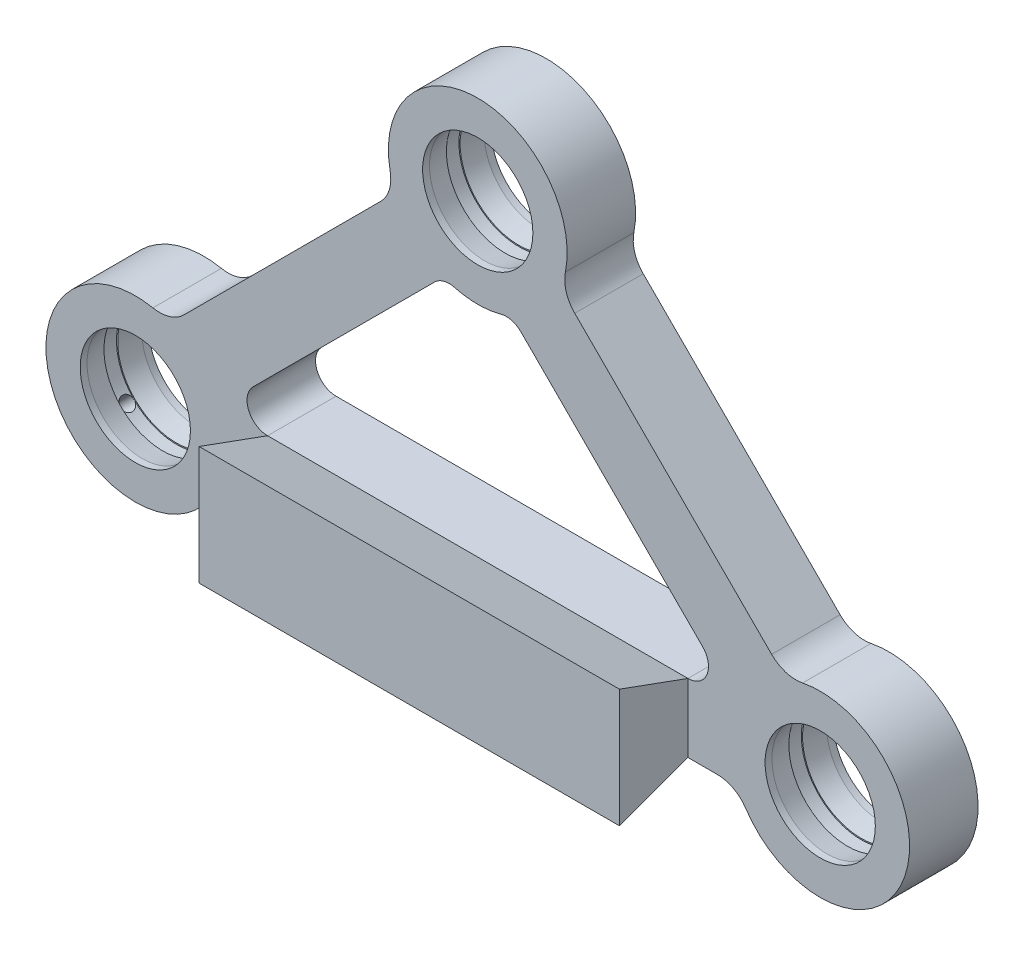
SolidWorks part; units mm, degrees
material "ABS"
ref_plane "Front Plane" through (0, 0, 0) normal (0, 0, 1) x (1, 0, 0)
ref_plane "Top Plane" through (0, 0, 0) normal (0, 1, 0) x (1, 0, 0)
ref_plane "Right Plane" through (0, 0, 0) normal (1, 0, 0) x (0, 0, -1)
sketch "Sketch1" plane through (0, 0, 0) normal (0, 0, 1) x (1, 0, 0)
  line L0 (-26.538, 0) -> (73.462, 0) construction
  line L2 (-26.538, 0) -> (23.462, 50) construction
  line L3 (23.462, 50) -> (73.462, 0) construction
  line L4 (-14.4839, 5) -> (61.4078, 5)
  line L5 (-14.4839, -5) -> (61.4078, -5)
  line L6 (-21.55, 12.0591) -> (11.4029, 45.012)
  line L7 (18.474, 37.9409) -> (-14.4789, 4.988)
  line L8 (28.45, 37.9409) -> (61.4029, 4.988)
  line L9 (35.5211, 45.012) -> (68.474, 12.0591)
  circle A0 centre (23.462, 50) radius 8.05
  circle A1 centre (73.462, 0) radius 8.05
  circle A2 centre (-26.538, 0) radius 8.05
  circle A3 centre (-26.538, 0) radius 13.05
  circle A4 centre (23.462, 50) radius 13.05
  circle A5 centre (73.462, 0) radius 13.05
  dimension "D1" = 16.1
  dimension "D2" = 16.1
  dimension "D3" = 16.1
  dimension "D4" = 45
  dimension "D5" = 45
  dimension "D6" = 100
  dimension "D7" = 5
  dimension "D8" = 5
  dimension "D9" = 5
  dimension "D10" = 5
  dimension "D11" = 5
  dimension "D12" = 5
  dimension "D13" = 5
  dimension "D14" = 5
  dimension "D15" = 5
extrude "Boss-Extrude1" add sketch "Sketch1" along normal blind 8 contours A3 A2 | A4 L6 A3 L4 L7 | A4 A0 | A5 L9 A4 L8 L4 | A5 L8 L4 L7 A3 L5 | A5 A1 | A3 L7 L4 | A5 L4 L8 region at (-1.538, 25, 0) region at (-14.4766, 4.996, 0) region at (-14.8224, 4.8528, 0) region at (23.462, 0, 0) region at (48.462, 25, 0) region at (61.4006, 4.996, 0) region at (14.4953, 41.0333, 0) region at (64.4997, 8.9712, 0)
sketch3d "3DSketch1" plane through (0, 0, 0) normal (0, 0, 1) x (1, 0, 0)
  dimension "D1" = 4
sketch "Sketch3" plane through (0, 0, 4) normal (0, 0, 1) x (1, 0, 0)
  circle A0 centre (-26.538, 0) radius 8.7553
  circle A1 centre (23.462, 50) radius 8.7553
  circle A2 centre (73.462, 0) radius 8.7553
  circle A3 centre (-26.538, 0) radius 8.05 construction
  circle A4 centre (23.462, 50) radius 8.05 construction
  circle A5 centre (73.462, 0) radius 8.05 construction
  dimension "D1" = 0.7053
  dimension "D2" = 0.7053
  dimension "D3" = 0.7053
extrude "Cut-Extrude1" cut sketch "Sketch3" against normal blind 1 and the other way blind 1 contours A1 | A0 | A2
sketch3d "3DSketch2" plane through (0, 0, 0) normal (0, 0, 1) x (1, 0, 0)
sketch3d "3DSketch3" plane through (0, 0, 0) normal (0, 0, 1) x (1, 0, 0)
  dimension "D1" = 26
sketch "Sketch4" plane through (0, 62.95, 0) normal (0, -1, 0) x (-1, 0, 0)
  line L0 (-41.8, -4) -> (41.8, -4) construction
  line L1 (-86.512, 0) -> (-86.512, -8) construction
  line L4 (-36.5118, -8) -> (-68.474, -8)
  line L5 (-36.5118, -8) -> (-68.474, -8)
  line L6 (-68.474, -8) -> (-86.512, -8)
  line L7 (-68.474, -8) -> (-86.512, -8)
  line L8 (-86.512, -8) -> (-86.512, 0)
  line L9 (-86.512, -8) -> (-86.512, 0)
  line L10 (-86.512, 0) -> (-68.474, 0)
  line L11 (-86.512, 0) -> (-68.474, 0)
  line L12 (-68.474, 0) -> (-36.5118, 0)
  line L13 (-68.474, 0) -> (-36.5118, 0)
  line L14 (-36.5118, 0) -> (-10.4122, 0)
  line L15 (-36.5118, 0) -> (-10.4122, 0)
  line L16 (-10.4122, 0) -> (21.55, 0)
  line L17 (-10.4122, 0) -> (21.55, 0)
  line L18 (21.55, 0) -> (39.588, 0)
  line L19 (21.55, 0) -> (39.588, 0)
  line L20 (39.588, 0) -> (39.588, -8)
  line L21 (39.588, 0) -> (39.588, -8)
  line L22 (39.588, -8) -> (21.55, -8)
  line L23 (39.588, -8) -> (21.55, -8)
  line L24 (21.55, -8) -> (-10.4122, -8)
  line L25 (21.55, -8) -> (-10.4122, -8)
  line L26 (-10.4122, -8) -> (-36.5118, -8)
  line L27 (-10.4122, -8) -> (-36.5118, -8)
  circle A0 centre (-23.462, -4) radius 1
  dimension "D1" = 2
  dimension "D2" = 63.05
  dimension "D3" = 126.1
extrude "Cut-Extrude2" cut sketch "Sketch4" along normal blind 6 contours A0
fillet "Fillet1" radius 3 4 edges at (-14.4669, 5, 4) (18.474, 37.9409, 4) (28.45, 37.9409, 4) (61.3909, 5, 4)
fillet "Fillet2" radius 5 6 edges at (68.474, 12.0591, 4) (35.5211, 45.012, 4) (11.4029, 45.012, 4) (-21.55, 12.0591, 4) (-14.4839, -5, 4) (61.4078, -5, 4)
sketch3d "3DSketch4" plane through (0, 0, 0) normal (0, 0, 1) x (1, 0, 0)
sketch3d "3DSketch5" plane through (0, 0, 0) normal (0, 0, 1) x (1, 0, 0)
  dimension "D1" = 26
sketch "Sketch5" plane through (45.888, -45.888, 0) normal (-0.7071, 0.7071, 0) x (0, 0, 1)
  line L0 (8, -31.8152) -> (8, -7.901) construction
  line L1 (8, 43.8955) -> (8, 59.9955) construction
  line L2 (8, 43.8955) -> (8, 59.9955)
  line L7 (8, 64.9955) -> (0, 64.9955) construction
  line L8 (8, 64.9955) -> (0, 64.9955)
  circle A0 centre (4, 51.9455) radius 1
  dimension "D1" = 2
  dimension "D2" = 4
  dimension "D3" = 8.05
  dimension "D4" = 16.1
extrude "Cut-Extrude3" cut sketch "Sketch5" along normal blind 10 contours A0 region at (82.619, -9.157, 4)
draft "Draft4" type of draft neutral plane draft angle 10 faces to draft 3 face at (-18.488, 0, 5) face at (31.512, 50, 5) face at (81.512, 0, 5) neutral plane through (0, 0, 8) neutral plane normal (0, 0, 1) reverse direction yes parameters "D1"=10
draft "Draft6" type of draft neutral plane draft angle 10 faces to draft 3 face at (-18.488, 0, 0) face at (81.512, 0, 0) face at (31.512, 50, 0) neutral plane through (0, 0, 0) neutral plane normal (0, 0, -1) reverse direction yes parameters "D1"=10
sketch3d "3DSketch6" plane through (0, 0, 0) normal (0, 0, 1) x (1, 0, 0)
sketch3d "3DSketch8" plane through (0, 0, 0) normal (0, 0, 1) x (1, 0, 0)
  dimension "D1" = 26
sketch "Sketch6" plane through (-22.426, -22.426, 0) normal (0.7071, 0.7071, 0) x (0, 0, -1)
  line L0 (-8, 31.8152) -> (-8, 5.7152) construction
  line L1 (0, 31.8152) -> (-8, 31.8152) construction
  line L2 (0, 31.8152) -> (-8, 31.8152)
  line L3 (0, 10.7152) -> (0, 26.8152) construction
  line L4 (0, 10.7152) -> (0, 26.8152)
  circle A0 centre (-4, 18.7652) radius 1
  dimension "D1" = 2
  dimension "D2" = 4
  dimension "D4" = 16.1
  dimension "D5" = 8.05
extrude "Cut-Extrude4" cut sketch "Sketch6" along normal blind 10 contours A0
sketch "Sketch7" plane through (0, 0, 8) normal (0, 0, 1) x (1, 0, 0)
  line L2 (-7.2243, 5) -> (54.1483, 5) construction
  line L5 (17.1588, 36.6257) -> (-9.3456, 10.1213) construction
  line L10 (29.7652, 36.6257) -> (56.2696, 10.1213) construction
  line L11 (66.372, 14.161) -> (37.623, 42.91)
  line L12 (9.301, 42.91) -> (-19.448, 14.161)
  line L13 (-11.5113, -5) -> (58.4353, -5)
  line L14 (66.372, 14.161) -> (37.623, 42.91)
  line L15 (9.301, 42.91) -> (-19.448, 14.161)
  line L16 (-11.5113, -5) -> (58.4353, -5)
  line L17 (-7.2243, 5) -> (54.1483, 5)
  line L18 (17.1588, 36.6257) -> (-9.3456, 10.1213)
  line L19 (29.7652, 36.6257) -> (56.2696, 10.1213)
  circle A36 centre (-26.538, 0) radius 8.05 construction
  arc A37 (-9.3456, 10.1213) -> (-7.2243, 5) centre (-7.2243, 8) ccw construction
  arc A38 (54.1483, 5) -> (56.2696, 10.1213) centre (54.1483, 8) ccw construction
  circle A39 centre (73.462, 0) radius 8.05 construction
  circle A40 centre (23.462, 50) radius 8.05 construction
  arc A41 (29.7652, 36.6257) -> (26.8622, 37.4008) centre (27.6439, 34.5044) ccw construction
  arc A42 (20.0618, 37.4008) -> (26.8622, 37.4008) centre (23.462, 50) ccw construction
  arc A43 (20.0618, 37.4008) -> (17.1588, 36.6257) centre (19.2801, 34.5044) ccw construction
  circle A44 centre (-26.538, 0) radius 8.05
  arc A45 (36.2565, 47.4302) -> (37.623, 42.91) centre (41.1586, 46.4456) ccw
  arc A46 (36.2565, 47.4302) -> (10.6675, 47.4302) centre (23.462, 50) ccw
  arc A47 (9.301, 42.91) -> (10.6675, 47.4302) centre (5.7654, 46.4456) ccw
  arc A48 (-23.9682, 12.7945) -> (-19.448, 14.161) centre (-22.9836, 17.6966) ccw
  arc A49 (-23.9682, 12.7945) -> (-15.6738, -7.2299) centre (-26.538, 0) ccw
  arc A50 (-11.5113, -5) -> (-15.6738, -7.2299) centre (-11.5113, -10) ccw
  arc A51 (62.5978, -7.2299) -> (58.4353, -5) centre (58.4353, -10) ccw
  arc A52 (62.5978, -7.2299) -> (70.8922, 12.7945) centre (73.462, 0) ccw
  arc A53 (66.372, 14.161) -> (70.8922, 12.7945) centre (69.9076, 17.6966) ccw
  arc A54 (36.2565, 47.4302) -> (37.623, 42.91) centre (41.1586, 46.4456) ccw
  arc A55 (36.2565, 47.4302) -> (10.6675, 47.4302) centre (23.462, 50) ccw
  arc A56 (9.301, 42.91) -> (10.6675, 47.4302) centre (5.7654, 46.4456) ccw
  arc A57 (-23.9682, 12.7945) -> (-19.448, 14.161) centre (-22.9836, 17.6966) ccw
  arc A58 (-23.9682, 12.7945) -> (-15.6738, -7.2299) centre (-26.538, 0) ccw
  arc A59 (-11.5113, -5) -> (-15.6738, -7.2299) centre (-11.5113, -10) ccw
  arc A60 (62.5978, -7.2299) -> (58.4353, -5) centre (58.4353, -10) ccw
  arc A61 (62.5978, -7.2299) -> (70.8922, 12.7945) centre (73.462, 0) ccw
  arc A62 (66.372, 14.161) -> (70.8922, 12.7945) centre (69.9076, 17.6966) ccw
  arc A63 (-9.3456, 10.1213) -> (-7.2243, 5) centre (-7.2243, 8) ccw
  arc A64 (54.1483, 5) -> (56.2696, 10.1213) centre (54.1483, 8) ccw
  circle A65 centre (73.462, 0) radius 8.05
  circle A66 centre (23.462, 50) radius 8.05
  arc A67 (29.7652, 36.6257) -> (26.8622, 37.4008) centre (27.6439, 34.5044) ccw
  arc A68 (20.0618, 37.4008) -> (26.8622, 37.4008) centre (23.462, 50) ccw
  arc A69 (20.0618, 37.4008) -> (17.1588, 36.6257) centre (19.2801, 34.5044) ccw
  dimension "D1" = 0
extrude "Boss-Extrude3" add sketch "Sketch7" along normal blind 1
sketch "Sketch11" plane through (0, 0, 0) normal (0, 0, -1) x (-1, 0, 0)
  line L0 (-29.7652, 36.6257) -> (-56.2696, 10.1213) construction
  line L1 (7.2243, 5) -> (-54.1483, 5) construction
  line L2 (-17.1588, 36.6257) -> (9.3456, 10.1213) construction
  line L3 (-37.623, 42.91) -> (-66.372, 14.161)
  line L4 (-58.4353, -5) -> (11.5113, -5)
  line L5 (19.448, 14.161) -> (-9.301, 42.91)
  line L6 (-37.623, 42.91) -> (-66.372, 14.161)
  line L7 (-58.4353, -5) -> (11.5113, -5)
  line L8 (19.448, 14.161) -> (-9.301, 42.91)
  line L9 (-17.1588, 36.6257) -> (9.3456, 10.1213)
  line L10 (7.2243, 5) -> (-54.1483, 5)
  line L11 (-29.7652, 36.6257) -> (-56.2696, 10.1213)
  circle A0 centre (-23.462, 50) radius 8.05 construction
  circle A1 centre (-73.462, 0) radius 8.05
  circle A2 centre (-73.462, 0) radius 8.05
  circle A3 centre (-23.462, 50) radius 8.05
  circle A4 centre (26.538, 0) radius 8.05 construction
  circle A5 centre (26.538, 0) radius 8.05
  arc A6 (-17.1588, 36.6257) -> (-20.0618, 37.4008) centre (-19.2801, 34.5044) ccw construction
  arc A7 (-26.8622, 37.4008) -> (-20.0618, 37.4008) centre (-23.462, 50) ccw construction
  arc A8 (-26.8622, 37.4008) -> (-29.7652, 36.6257) centre (-27.6439, 34.5044) ccw construction
  arc A9 (-56.2696, 10.1213) -> (-54.1483, 5) centre (-54.1483, 8) ccw construction
  arc A10 (7.2243, 5) -> (9.3456, 10.1213) centre (7.2243, 8) ccw construction
  arc A11 (-10.6675, 47.4302) -> (-36.2565, 47.4302) centre (-23.462, 50) ccw
  arc A12 (-37.623, 42.91) -> (-36.2565, 47.4302) centre (-41.1586, 46.4456) ccw
  arc A13 (-70.8922, 12.7945) -> (-66.372, 14.161) centre (-69.9076, 17.6966) ccw
  arc A14 (-70.8922, 12.7945) -> (-62.5978, -7.2299) centre (-73.462, 0) ccw
  arc A15 (-58.4353, -5) -> (-62.5978, -7.2299) centre (-58.4353, -10) ccw
  arc A16 (15.6738, -7.2299) -> (11.5113, -5) centre (11.5113, -10) ccw
  arc A17 (15.6738, -7.2299) -> (23.9682, 12.7945) centre (26.538, 0) ccw
  arc A18 (19.448, 14.161) -> (23.9682, 12.7945) centre (22.9836, 17.6966) ccw
  arc A19 (-10.6675, 47.4302) -> (-9.301, 42.91) centre (-5.7654, 46.4456) ccw
  arc A20 (-10.6675, 47.4302) -> (-36.2565, 47.4302) centre (-23.462, 50) ccw
  arc A21 (-37.623, 42.91) -> (-36.2565, 47.4302) centre (-41.1586, 46.4456) ccw
  arc A22 (-70.8922, 12.7945) -> (-66.372, 14.161) centre (-69.9076, 17.6966) ccw
  arc A23 (-70.8922, 12.7945) -> (-62.5978, -7.2299) centre (-73.462, 0) ccw
  arc A24 (-58.4353, -5) -> (-62.5978, -7.2299) centre (-58.4353, -10) ccw
  arc A25 (15.6738, -7.2299) -> (11.5113, -5) centre (11.5113, -10) ccw
  arc A26 (15.6738, -7.2299) -> (23.9682, 12.7945) centre (26.538, 0) ccw
  arc A27 (19.448, 14.161) -> (23.9682, 12.7945) centre (22.9836, 17.6966) ccw
  arc A28 (-10.6675, 47.4302) -> (-9.301, 42.91) centre (-5.7654, 46.4456) ccw
  arc A29 (7.2243, 5) -> (9.3456, 10.1213) centre (7.2243, 8) ccw
  arc A30 (-56.2696, 10.1213) -> (-54.1483, 5) centre (-54.1483, 8) ccw
  arc A31 (-26.8622, 37.4008) -> (-29.7652, 36.6257) centre (-27.6439, 34.5044) ccw
  arc A32 (-26.8622, 37.4008) -> (-20.0618, 37.4008) centre (-23.462, 50) ccw
  arc A33 (-17.1588, 36.6257) -> (-20.0618, 37.4008) centre (-19.2801, 34.5044) ccw
  dimension "D1" = 0
  dimension "D2" = 0
extrude "Boss-Extrude4" add sketch "Sketch11" along normal blind 1
sketch "Sketch13" plane through (0, 0, 0) normal (1, 0, 0) x (0, 0, -1)
  line L0 (-9, 5) -> (-19, 8.6397)
  line L1 (-19, 8.6397) -> (-19, -8.6397)
  line L2 (-19, -8.6397) -> (-9, -5)
  line L3 (-19, 0) -> (-9, 0)
  line L4 (-9, 8.05) -> (-9, -8.05) construction
  line L5 (-9, 5) -> (-9, -5)
  dimension "D1" = 70
  dimension "D2" = 10
extrude "Boss-Extrude6" add sketch "Sketch13" against normal up to vertex (7.2243 mm away) and the other way up to vertex (54.1483 mm away) contours L5 L0 L1 L3 | L5 L3 L1 L2 region at (0, 3.4909, 14.4447) region at (0, -3.4909, 14.4447) up to point (-7.2243, 5, 9) other way up to point (54.1483, 5, 9)
equation "\"D2@Sketch1\"=\"D1@Sketch1\""
equation "\"D3@Sketch1\"=\"D1@Sketch1\""
equation "\"D5@Sketch1\"=\"D4@Sketch1\""
equation "\"D8@Sketch1\"=\"D7@Sketch1\""
equation "\"D9@Sketch1\"=\"D7@Sketch1\""
equation "\"D11@Sketch1\"=\"D10@Sketch1\""
equation "\"D12@Sketch1\"=\"D10@Sketch1\""
equation "\"D13@Sketch1\"=\"D10@Sketch1\""
equation "\"D14@Sketch1\"=\"D13@Sketch1\""
equation "\"D15@Sketch1\"=\"D14@Sketch1\""
equation "\"D2@Sketch3\"=\"D1@Sketch3\""
equation "\"D3@Sketch3\"=\"D1@Sketch3\""
equation "\"D2@Sketch4\"=\"D3@Sketch4\"/2"
equation "\"D3@Sketch5\"=\"D4@Sketch5\"/2"
equation "\"D2@Sketch5\"=\"D5@Sketch5\"/2"
equation "\"D2@Sketch6\"=\"D3@Sketch6\"/2"
equation "\"D5@Sketch6\"=\"D4@Sketch6\"/2"
equation "\"D1@Sketch3\"=4*tan(10)"
